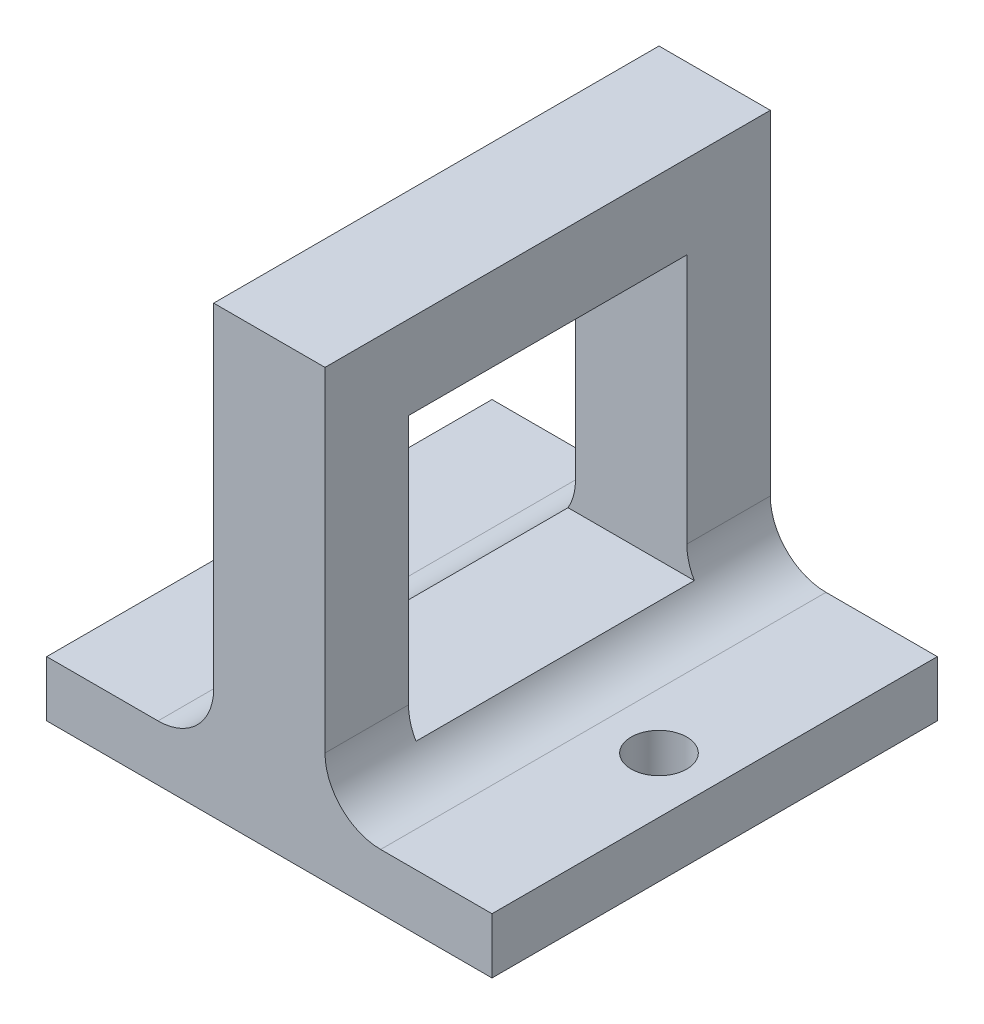
SolidWorks part; units mm, degrees
material "ABS"
ref_plane "Front Plane" through (0, 0, 0) normal (0, 0, 1) x (1, 0, 0)
ref_plane "Top Plane" through (0, 0, 0) normal (0, 1, 0) x (1, 0, 0)
ref_plane "Right Plane" through (0, 0, 0) normal (1, 0, 0) x (0, 0, -1)
sketch "Sketch1" plane through (0, 0, 0) normal (1, 0, 0) x (0, 0, -1)
  line L0 (0, -25.4) -> (0, 0) construction
  line L1 (-25.4, -25.4) -> (25.4, -25.4)
  line L2 (-25.4, -25.4) -> (-25.4, 25.4)
  line L3 (-25.4, 25.4) -> (25.4, 25.4)
  line L4 (25.4, -25.4) -> (25.4, 25.4)
  line L5 (-25.4, -25.4) -> (25.4, 25.4) construction
  line L6 (-25.4, 25.4) -> (25.4, -25.4) construction
  line L8 (-15.875, -15.875) -> (15.875, -15.875)
  line L9 (-15.875, -15.875) -> (-15.875, 15.875)
  line L10 (-15.875, 15.875) -> (15.875, 15.875)
  line L11 (15.875, -15.875) -> (15.875, 15.875)
  line L12 (-15.875, -15.875) -> (15.875, 15.875) construction
  line L13 (-15.875, 15.875) -> (15.875, -15.875) construction
  point P0 (0, 0)
  dimension "D1" = 50.8
  dimension "D2" = 50.8
  dimension "D3" = 25.4
  dimension "D4" = 31.75
  dimension "D5" = 31.75
extrude "Boss-Extrude1" add sketch "Sketch1" along normal mid plane 12.7
sketch "Sketch2" plane through (0, 0, 0) normal (1, 0, 0) x (0, 0, -1)
  line L0 (25.4, -25.4) -> (25.4, 25.4) construction
  line L1 (-25.4, -25.4) -> (25.4, -25.4)
  line L2 (-25.4, -25.4) -> (-25.4, -19.05)
  line L3 (-25.4, -19.05) -> (25.4, -19.05)
  line L4 (25.4, -25.4) -> (25.4, -19.05)
  dimension "D1" = 6.35
extrude "Boss-Extrude2" add sketch "Sketch2" along normal mid plane 50.8
fillet "Fillet1" radius 6.35 2 edges at (-6.35, -19.05, 0) (6.35, -19.05, 0)
sketch "Sketch3" plane through (0, -19.05, 0) normal (0, 1, 0) x (1, 0, 0)
  line L0 (25.4, -25.4) -> (12.7, -25.4) construction
  line L1 (25.4, 25.4) -> (25.4, -25.4) construction
  circle A0 centre (19.05, 0) radius 3.175
  dimension "D1" = 6.35
  dimension "D2" = 25.4
  dimension "D3" = 6.35
extrude "Cut-Extrude1" cut sketch "Sketch3" against normal through all
mirror "Mirror1" about plane through (0, 0, 0) normal (1, 0, 0) of "Cut-Extrude1"
